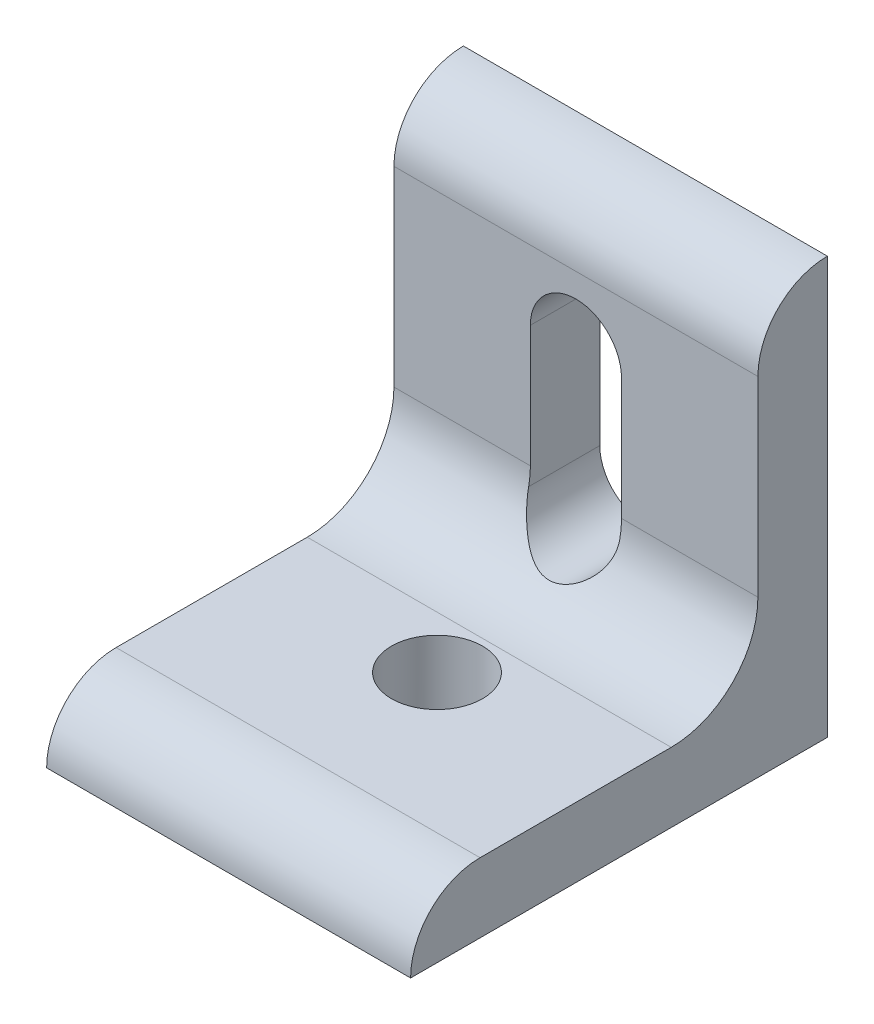
SolidWorks part; units mm, degrees
ref_plane "Front Plane" through (0, 0, 0) normal (0, 0, 1) x (1, 0, 0)
ref_plane "Top Plane" through (0, 0, 0) normal (0, 1, 0) x (1, 0, 0)
ref_plane "Right Plane" through (0, 0, 0) normal (1, 0, 0) x (0, 0, -1)
ref_plane "Plane1" through (-16.637, 0, 0) normal (-1, 0, 0) x (0, -1, 0)
sketch "Sketch1" plane through (-16.637, 0, 0) normal (-1, 0, 0) x (0, -1, 0)
  line L0 (-6.35, 31.75) -> (-6.35, 6.35)
  line L1 (-6.35, 6.35) -> (-31.75, 6.35)
  line L2 (-38.1, 0) -> (0, 0)
  line L3 (0, 0) -> (0, 38.1)
  arc A0 (0, 38.1) -> (-6.35, 31.75) centre (0, 31.75) ccw
  arc A1 (-31.75, 6.35) -> (-38.1, 0) centre (-31.75, 0) ccw
extrude "Boss-Extrude1" add sketch "Sketch1" against normal blind 33.274
sketch "Sketch2" plane through (0, 0, 6.35) normal (0, 0, 1) x (1, 0, 0)
  line L0 (4.1656, 12.7) -> (4.1656, 25.4)
  line L1 (-4.1656, 25.4) -> (-4.1656, 12.7)
  arc A0 (-4.1656, 12.7) -> (4.1656, 12.7) centre (0, 12.7) ccw
  arc A1 (4.1656, 25.4) -> (-4.1656, 25.4) centre (0, 25.4) ccw
extrude "Cut-Extrude1" cut sketch "Sketch2" against normal through all
hole_wizard "5/16 Clearance Hole1" positions "Sketch4" profile "Sketch3" hole size "5/16" standard "ANSI Inch"
sketch "Sketch4" plane through (0, 0, 0) normal (0, -1, 0) x (-1, 0, 0)
  point P0 (0, -19.05)
sketch "Sketch3" plane through (0, 0, 19.05) normal (1, 0, 0) x (0, 0, -1)
  line L0 (0, 0) -> (0, 38.1)
  line L1 (0, 38.1) -> (4.1656, 38.1)
  line L2 (4.1656, 38.1) -> (4.1656, 0)
  line L5 (4.1656, 0) -> (0, 0)
  line L11 (0, -6.35) -> (0, 107.95) construction
  dimension "Thru Hole Dia." = 8.3312
  dimension "Thru Hole Depth" = 38.1
fillet "Fillet1" radius 7.9248 1 edges at (0, 6.35, 6.35) tangent propagation no
